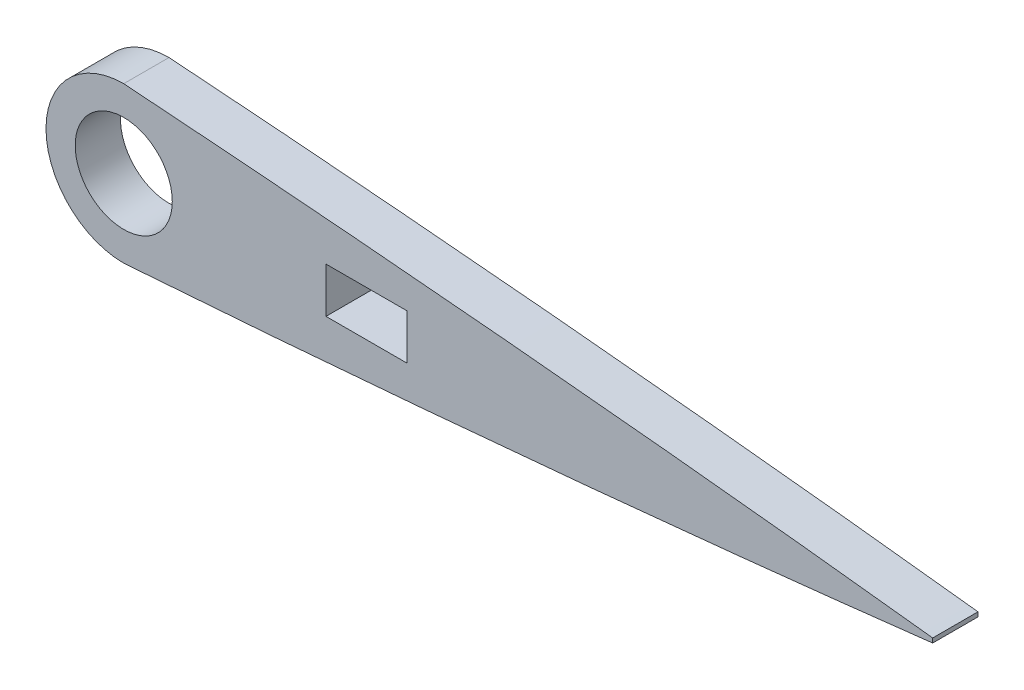
SolidWorks part; units mm, degrees
material "Фанера"
ref_plane "Спереди" through (0, 0, 0) normal (0, 0, 1) x (1, 0, 0)
ref_plane "Сверху" through (0, 0, 0) normal (0, 1, 0) x (1, 0, 0)
ref_plane "Справа" through (0, 0, 0) normal (1, 0, 0) x (0, 0, -1)
curve "Кривая1"
  spline degree 3 poles (200, 0.1365, 0) (199.688, 0.1729, 0) (198.8167, 0.2745, 0) (197.2359, 0.4561, 0) (195.145, 0.6923, 0) (192.7015, 0.9625, 0) (189.9816, 1.2561, 0) (187.0365, 1.566, 0) (183.905, 1.8867, 0) (180.6179, 2.2137, 0) (177.2012, 2.5436, 0) (173.6771, 2.8733, 0) (170.065, 3.2002, 0) (166.3822, 3.5221, 0) (162.6444, 3.8368, 0) (158.8659, 4.1424, 0) (155.06, 4.437, 0) (151.2387, 4.7189, 0) (147.4135, 4.9862, 0) (143.595, 5.2374, 0) (139.7935, 5.4706, 0) (136.0183, 5.6841, 0) (132.2786, 5.8765, 0) (128.5831, 6.0459, 0) (124.94, 6.191, 0) (121.3572, 6.3103, 0) (117.8424, 6.4025, 0) (114.4029, 6.4663, 0) (111.0457, 6.5008, 0) (107.7777, 6.505, 0) (104.6056, 6.4782, 0) (101.5356, 6.4201, 0) (98.5742, 6.3302, 0) (95.7272, 6.2086, 0) (93.0006, 6.0555, 0) (90.4002, 5.8711, 0) (87.9314, 5.6561, 0) (85.5998, 5.4114, 0) (83.4106, 5.1378, 0) (81.3691, 4.8365, 0) (79.4802, 4.5088, 0) (77.7488, 4.156, 0) (76.1798, 3.7796, 0) (74.7776, 3.3811, 0) (73.5467, 2.9618, 0) (72.4905, 2.523, 0) (71.6134, 2.0657, 0) (70.9148, 1.5895, 0) (70.4055, 1.0913, 0) (70.0654, 0.5615, 0) (70.0211, 0.181, 0) (70, 0, 0) knots 0 0 0 0 0.007145 0.019956 0.036196 0.055011 0.075879 0.098429 0.122376 0.147488 0.173572 0.20046 0.228005 0.256076 0.284555 0.313333 0.34231 0.371393 0.400496 0.429538 0.458442 0.487136 0.515552 0.543624 0.57129 0.598491 0.62517 0.651272 0.676746 0.701542 0.725611 0.748908 0.771388 0.793008 0.813728 0.833508 0.85231 0.870097 0.886836 0.902493 0.917037 0.930441 0.94268 0.953734 0.96359 0.972247 0.979722 0.986065 0.991385 0.995901 1 1 1 1
curve "Кривая2"
  spline degree 3 poles (70, 0, 0) (70.0211, -0.181, 0) (70.0654, -0.5615, 0) (70.4055, -1.0913, 0) (70.9148, -1.5895, 0) (71.6134, -2.0657, 0) (72.4905, -2.523, 0) (73.5467, -2.9618, 0) (74.7776, -3.3811, 0) (76.1798, -3.7796, 0) (77.7488, -4.156, 0) (79.4802, -4.5088, 0) (81.3691, -4.8365, 0) (83.4106, -5.1378, 0) (85.5998, -5.4114, 0) (87.9314, -5.6561, 0) (90.4002, -5.8711, 0) (93.0006, -6.0555, 0) (95.7272, -6.2086, 0) (98.5742, -6.3302, 0) (101.5356, -6.4201, 0) (104.6056, -6.4782, 0) (107.7777, -6.505, 0) (111.0457, -6.5008, 0) (114.4029, -6.4663, 0) (117.8424, -6.4025, 0) (121.3572, -6.3103, 0) (124.94, -6.191, 0) (128.5831, -6.0459, 0) (132.2786, -5.8765, 0) (136.0183, -5.6841, 0) (139.7935, -5.4706, 0) (143.595, -5.2374, 0) (147.4135, -4.9862, 0) (151.2387, -4.7189, 0) (155.06, -4.437, 0) (158.8659, -4.1424, 0) (162.6444, -3.8368, 0) (166.3822, -3.5221, 0) (170.065, -3.2002, 0) (173.6771, -2.8733, 0) (177.2012, -2.5436, 0) (180.6179, -2.2137, 0) (183.905, -1.8867, 0) (187.0365, -1.566, 0) (189.9816, -1.2561, 0) (192.7015, -0.9625, 0) (195.145, -0.6923, 0) (197.2359, -0.4561, 0) (198.8167, -0.2745, 0) (199.688, -0.1729, 0) (200, -0.1365, 0) knots 0 0 0 0 0.004099 0.008615 0.013935 0.020278 0.027753 0.03641 0.046266 0.05732 0.069559 0.082963 0.097507 0.113164 0.129903 0.14769 0.166492 0.186272 0.206992 0.228612 0.251092 0.274389 0.298458 0.323254 0.348728 0.37483 0.401509 0.42871 0.456376 0.484448 0.512864 0.541558 0.570462 0.599504 0.628607 0.65769 0.686667 0.715445 0.743924 0.771995 0.79954 0.826428 0.852512 0.877624 0.901571 0.924121 0.944989 0.963804 0.980044 0.992855 1 1 1 1
sketch "Эскиз1" plane through (0, 0, 0) normal (0, 0, 1) x (1, 0, 0)
  line L0 (200, 0.1365) -> (200, -0.1365)
  line L1 (100.4, -6.3839) -> (100.4, -3.2866)
  line L2 (100.4, -3.2866) -> (97.6, -3.2866)
  line L3 (97.6, -3.2866) -> (97.6, -6.2866)
  line L4 (124, 6.2207) -> (124, 3.116)
  line L5 (124, 3.116) -> (126.8, 3.116)
  line L6 (126.8, 3.116) -> (126.8, 6.116)
  line L8 (162.5, -1.4) -> (167.5, -1.4)
  line L9 (162.5, -1.4) -> (162.5, 1.4)
  line L10 (162.5, 1.4) -> (167.5, 1.4)
  line L11 (167.5, -1.4) -> (167.5, 1.4)
  line L12 (162.5, -1.4) -> (167.5, 1.4) construction
  line L13 (162.5, 1.4) -> (167.5, -1.4) construction
  circle A0 centre (109, 0) radius 4
  arc A1 (150, 4.8046) -> (150, -4.8046) centre (150, 0) ccw
  arc A2 (142.9507, 5.2753) -> (142.9507, -5.2753) centre (150, 0) ccw
  circle A4 centre (150, 0) radius 3
  spline S0 degree 3 poles (-2794.2878, -889.5298) (135.735, 36.6932) (65.8249, 6.0454) (70.4055, -1.0913) (70.9148, -1.5895) (71.6134, -2.0657) (72.4905, -2.523) (73.5467, -2.9618) (74.7776, -3.3811) (76.1798, -3.7796) (77.7488, -4.156) (79.4802, -4.5088) (81.3691, -4.8365) (83.4106, -5.1378) (85.5998, -5.4114) (87.9314, -5.6561) (90.4002, -5.8711) (93.0006, -6.0555) (95.7272, -6.2086) (98.5742, -6.3302) (101.5356, -6.4201) (104.6056, -6.4782) (107.7777, -6.505) (111.0457, -6.5008) (114.4029, -6.4663) (117.8424, -6.4025) (121.3572, -6.3103) (124.94, -6.191) (128.5831, -6.0459) (132.2786, -5.8765) (136.0183, -5.6841) (139.7935, -5.4706) (143.595, -5.2374) (147.4135, -4.9862) (151.2387, -4.7189) (155.06, -4.437) (158.8659, -4.1424) (162.6444, -3.8368) (166.3822, -3.5221) (170.065, -3.2002) (174.8191, -2.7699) (179.4417, -2.3307) (183.905, -1.8867) (187.0365, -1.566) (189.9816, -1.2561) (192.7015, -0.9625) (195.145, -0.6923) (197.2359, -0.4561) (276.563, 8.6571) (353.7675, 29.8587) (777.5475, -2938.4018) knots -0.173769 -0.173769 -0.173769 -0.173769 0.004099 0.008615 0.013935 0.020278 0.027753 0.03641 0.046266 0.05732 0.069559 0.082963 0.097507 0.113164 0.129903 0.14769 0.166492 0.186272 0.206992 0.228612 0.251092 0.274389 0.298458 0.323254 0.348728 0.37483 0.401509 0.42871 0.456376 0.484448 0.512864 0.541558 0.570462 0.599504 0.628607 0.65769 0.686667 0.715445 0.743924 0.771995 0.79954 0.852512 0.877624 0.901571 0.924121 0.944989 0.963804 0.980044 0.992855 2.780207 2.780207 2.780207 2.780207 only from (70, 0) to (200, -0.1365) construction
  spline S1 degree 3 poles (777.5457, 2938.3893) (353.7673, -29.8586) (276.5629, -8.657) (197.2359, 0.4561) (195.145, 0.6923) (192.7015, 0.9625) (189.9816, 1.2561) (187.0365, 1.566) (183.905, 1.8867) (179.4417, 2.3307) (174.8191, 2.7699) (170.065, 3.2002) (166.3822, 3.5221) (162.6444, 3.8368) (158.8659, 4.1424) (155.06, 4.437) (151.2387, 4.7189) (147.4135, 4.9862) (143.595, 5.2374) (139.7935, 5.4706) (136.0183, 5.6841) (132.2786, 5.8765) (128.5831, 6.0459) (124.94, 6.191) (121.3572, 6.3103) (117.8424, 6.4025) (114.4029, 6.4663) (111.0457, 6.5008) (107.7777, 6.505) (104.6056, 6.4782) (101.5356, 6.4201) (98.5742, 6.3302) (95.7272, 6.2086) (93.0006, 6.0555) (90.4002, 5.8711) (87.9314, 5.6561) (85.5998, 5.4114) (83.4106, 5.1378) (81.3691, 4.8365) (79.4802, 4.5088) (77.7488, 4.156) (76.1798, 3.7796) (74.7776, 3.3811) (73.5467, 2.9618) (72.4905, 2.523) (71.6134, 2.0657) (70.9148, 1.5895) (70.4055, 1.0913) (65.8251, -6.0451) (135.7293, -36.6906) (-2793.9197, 889.4134) knots -1.780204 -1.780204 -1.780204 -1.780204 0.007145 0.019956 0.036196 0.055011 0.075879 0.098429 0.122376 0.147488 0.20046 0.228005 0.256076 0.284555 0.313333 0.34231 0.371393 0.400496 0.429538 0.458442 0.487136 0.515552 0.543624 0.57129 0.598491 0.62517 0.651272 0.676746 0.701542 0.725611 0.748908 0.771388 0.793008 0.813728 0.833508 0.85231 0.870097 0.886836 0.902493 0.917037 0.930441 0.94268 0.953734 0.96359 0.972247 0.979722 0.986065 0.991385 0.995901 1.173762 1.173762 1.173762 1.173762 only from (200, 0.1365) to (70, 0) construction
  spline S2 degree 3 poles (70, 0) (70.0211, -0.181) (70.0654, -0.5615) (70.4055, -1.0913) (70.9148, -1.5895) (71.6134, -2.0657) (72.4905, -2.523) (73.5467, -2.9618) (74.7776, -3.3811) (76.1798, -3.7796) (77.7488, -4.156) (79.4802, -4.5088) (81.3691, -4.8365) (83.4106, -5.1378) (85.5998, -5.4114) (87.9314, -5.6561) (90.4002, -5.8711) (93.0006, -6.0555) (95.4152, -6.1911) (96.9625, -6.2607) (97.6, -6.2866) knots 0 0 0 0 0.004099 0.008615 0.013935 0.020278 0.027753 0.03641 0.046266 0.05732 0.069559 0.082963 0.097507 0.113164 0.129903 0.14769 0.166492 0.186272 0.206992 0.221505 0.221505 0.221505 0.221505
  spline S3 degree 3 poles (200, 0.1365) (199.688, 0.1729) (198.8167, 0.2745) (197.2359, 0.4561) (195.145, 0.6923) (192.7015, 0.9625) (189.9816, 1.2561) (187.0365, 1.566) (183.905, 1.8867) (179.4417, 2.3307) (174.8191, 2.7699) (170.065, 3.2002) (166.3822, 3.5221) (162.6444, 3.8368) (158.8659, 4.1424) (155.06, 4.437) (151.2387, 4.7189) (147.4135, 4.9862) (143.595, 5.2374) (139.7935, 5.4706) (136.0183, 5.6841) (132.2786, 5.8765) (129.2098, 6.0172) (127.3884, 6.0925) (126.8, 6.116) knots 0 0 0 0 0.007145 0.019956 0.036196 0.055011 0.075879 0.098429 0.122376 0.147488 0.20046 0.228005 0.256076 0.284555 0.313333 0.34231 0.371393 0.400496 0.429538 0.458442 0.487136 0.515552 0.543624 0.55702 0.55702 0.55702 0.55702
  spline S4 degree 3 poles (100.4, -6.3839) (100.7666, -6.3946) (102.157, -6.4319) (104.6056, -6.4782) (107.7777, -6.505) (111.0457, -6.5008) (114.4029, -6.4663) (117.8424, -6.4025) (121.3572, -6.3103) (124.94, -6.191) (128.5831, -6.0459) (132.2786, -5.8765) (136.0183, -5.6841) (139.7935, -5.4706) (143.595, -5.2374) (147.4135, -4.9862) (151.2387, -4.7189) (155.06, -4.437) (158.8659, -4.1424) (162.6444, -3.8368) (166.3822, -3.5221) (170.065, -3.2002) (174.8191, -2.7699) (179.4417, -2.3307) (183.905, -1.8867) (187.0365, -1.566) (189.9816, -1.2561) (192.7015, -0.9625) (195.145, -0.6923) (197.2359, -0.4561) (198.8167, -0.2745) (199.688, -0.1729) (200, -0.1365) knots 0.242749 0.242749 0.242749 0.242749 0.251092 0.274389 0.298458 0.323254 0.348728 0.37483 0.401509 0.42871 0.456376 0.484448 0.512864 0.541558 0.570462 0.599504 0.628607 0.65769 0.686667 0.715445 0.743924 0.771995 0.79954 0.852512 0.877624 0.901571 0.924121 0.944989 0.963804 0.980044 0.992855 1 1 1 1
  spline S5 degree 3 poles (124, 6.2207) (123.1115, 6.2516) (121.0507, 6.3184) (117.8424, 6.4025) (114.4029, 6.4663) (111.0457, 6.5008) (107.7777, 6.505) (104.6056, 6.4782) (101.5356, 6.4201) (98.5742, 6.3302) (95.7272, 6.2086) (93.0006, 6.0555) (90.4002, 5.8711) (87.9314, 5.6561) (85.5998, 5.4114) (83.4106, 5.1378) (81.3691, 4.8365) (79.4802, 4.5088) (77.7488, 4.156) (76.1798, 3.7796) (74.7776, 3.3811) (73.5467, 2.9618) (72.4905, 2.523) (71.6134, 2.0657) (70.9148, 1.5895) (70.4055, 1.0913) (70.0654, 0.5615) (70.0211, 0.181) (70, 0) knots 0.578266 0.578266 0.578266 0.578266 0.598491 0.62517 0.651272 0.676746 0.701542 0.725611 0.748908 0.771388 0.793008 0.813728 0.833508 0.85231 0.870097 0.886836 0.902493 0.917037 0.930441 0.94268 0.953734 0.96359 0.972247 0.979722 0.986065 0.991385 0.995901 1 1 1 1
  point P13 (99, -3.2866)
  point P18 (165, 0)
  dimension "D1" = 8
  dimension "D11" = 4.8046
  dimension "D12" = 8.8046
  dimension "D13" = 6
  dimension "D2" = 39
  dimension "D8" = 2.8
  dimension "D9" = 10
  dimension "D3" = 3
  dimension "D4" = 2.8
  dimension "D5" = 15
  dimension "D6" = 3
  dimension "D10" = 80
  dimension "D7" = 9.6092
  dimension "D14" = 5
  dimension "D15" = 2.8
  dimension "D16" = 15
extrude "Бобышка-Вытянуть1" add sketch "Эскиз1" along normal mid plane 2.8 contours A1 S4 L0 S3 A4 region at (199.4436, 0, 0)
equation "\"D11@Эскиз1\"=\"D7@Эскиз1\"/2"
equation "\"D12@Эскиз1\"=\"D11@Эскиз1\"+4"
